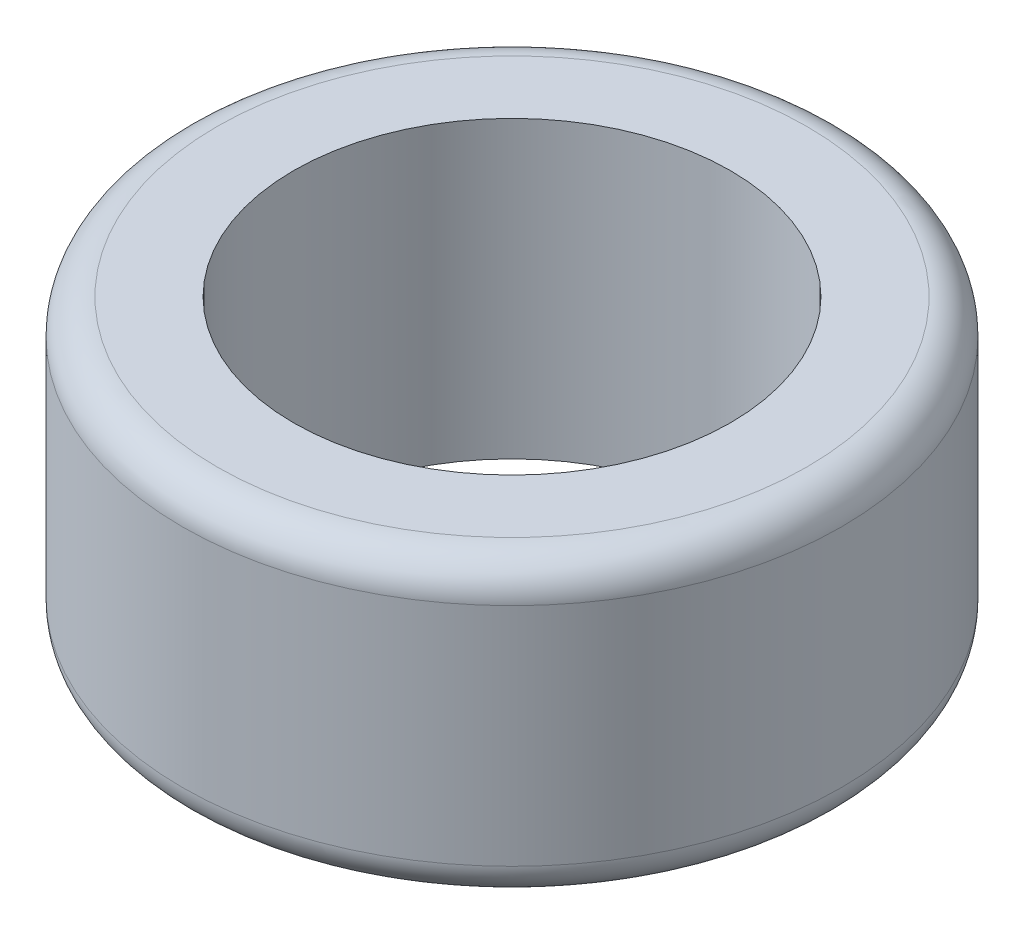
SolidWorks part; units mm, degrees
ref_plane "Front Plane" through (0, 0, 0) normal (0, 0, 1) x (1, 0, 0)
ref_plane "Top Plane" through (0, 0, 0) normal (0, 1, 0) x (1, 0, 0)
ref_plane "Right Plane" through (0, 0, 0) normal (1, 0, 0) x (0, 0, -1)
sketch "Sketch4" plane through (0, 0, 0) normal (0, 0, 1) x (1, 0, 0)
  line L0 (-152.4, 0) -> (-152.4, 205.74)
  line L1 (-152.4, 205.74) -> (-205.74, 205.74)
  line L2 (-152.4, 0) -> (-205.74, 0)
  line L3 (-229.87, 181.61) -> (-229.87, 24.13)
  line L4 (-152.4, 102.87) -> (-204.0709, 102.87) construction
  line L5 (0, 0) -> (0, 160.7909) construction
  arc A0 (-205.74, 205.74) -> (-229.87, 181.61) centre (-205.74, 181.61) ccw
  arc A1 (-229.87, 24.13) -> (-205.74, 0) centre (-205.74, 24.13) ccw
  point P11 (-229.87, 102.87)
  dimension "D1" = 205.74
  dimension "D2" = 157.48
  dimension "D3" = 229.87
  dimension "D4" = 152.4
revolve "Revolve1" add sketch "Sketch4" angle 360 about L5
ref_plane "Plane2" through (0, 102.87, 0) normal (0, -1, 0) x (-1, 0, 0)
